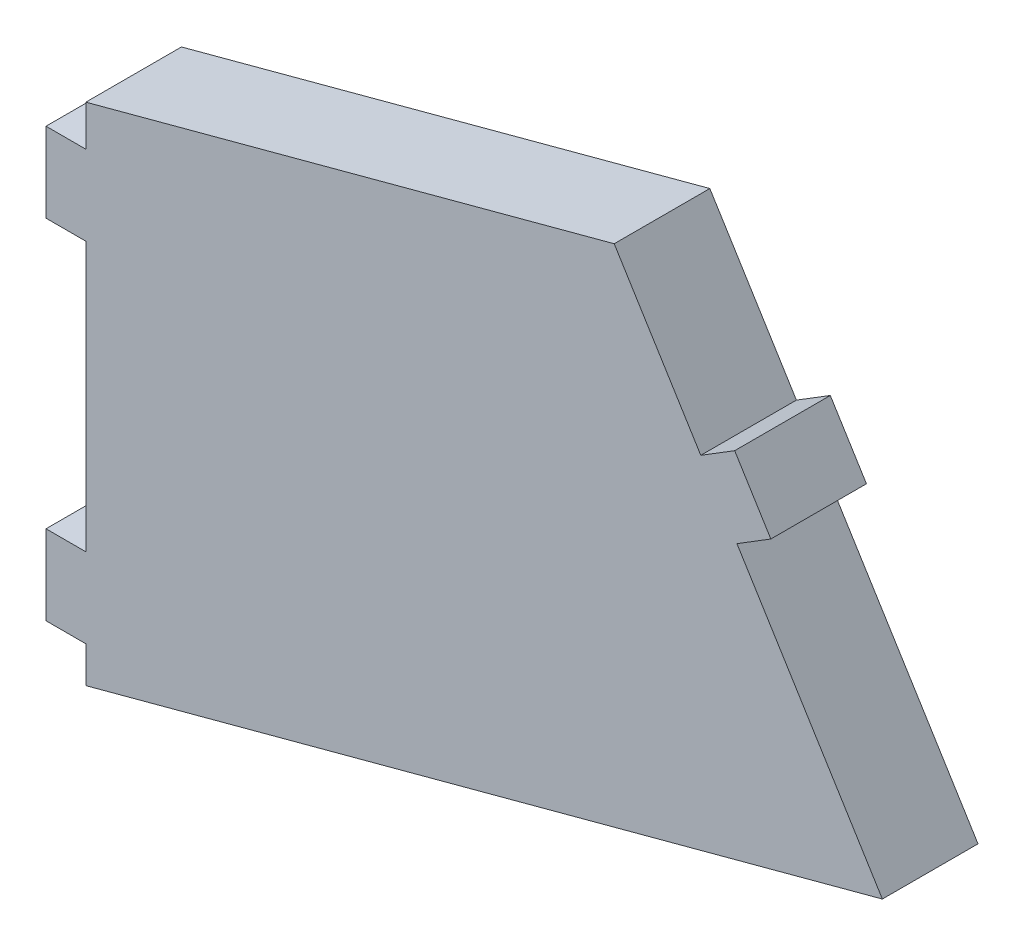
SolidWorks part; units mm, degrees
ref_plane "Front Plane" through (0, 0, 0) normal (0, 0, 1) x (1, 0, 0)
ref_plane "Top Plane" through (0, 0, 0) normal (0, 1, 0) x (1, 0, 0)
ref_plane "Right Plane" through (0, 0, 0) normal (1, 0, 0) x (0, 0, -1)
sketch "Sketch2" plane through (0, 0, 0) normal (0, 0, 1) x (1, 0, 0)
  line L0 (1.2422, 46.4634) -> (1.2422, 29.5883)
  line L1 (1.2422, 22.3149) -> (51.2194, 35.7062)
  line L2 (1.2422, 54.0201) -> (1.2422, 51.4634)
  line L3 (34.3936, 62.903) -> (39.8262, 54.1218)
  line L4 (39.8262, 54.1218) -> (41.9522, 55.4371)
  line L5 (1.2422, 51.4634) -> (-1.2578, 51.4634)
  line L6 (1.2422, 24.5883) -> (1.2422, 22.3149)
  line L7 (1.2422, 46.4634) -> (-1.2578, 46.4634)
  line L8 (-1.2578, 51.4634) -> (-1.2578, 46.4634)
  line L9 (1.2422, 29.5883) -> (-1.2578, 29.5883)
  line L10 (41.9522, 55.4371) -> (44.2202, 51.7713)
  line L11 (1.2422, 24.5883) -> (-1.2578, 24.5883)
  line L12 (-1.2578, 29.5883) -> (-1.2578, 24.5883)
  line L13 (44.2202, 51.7713) -> (42.0942, 50.456)
  line L14 (1.2422, 54.0201) -> (34.3936, 62.903)
  line L15 (42.0942, 50.456) -> (51.2194, 35.7062)
  dimension "D1" = 2.5567
  dimension "D2" = 5
  dimension "D4" = 5
  dimension "D6" = 2.2734
extrude "Boss-Extrude2" add sketch "Sketch2" against normal blind 6 contours L10 L13 L15 L1 L6 L11 L12 L9 L0 L7 L8 L5 L2 L14 L3 L4
